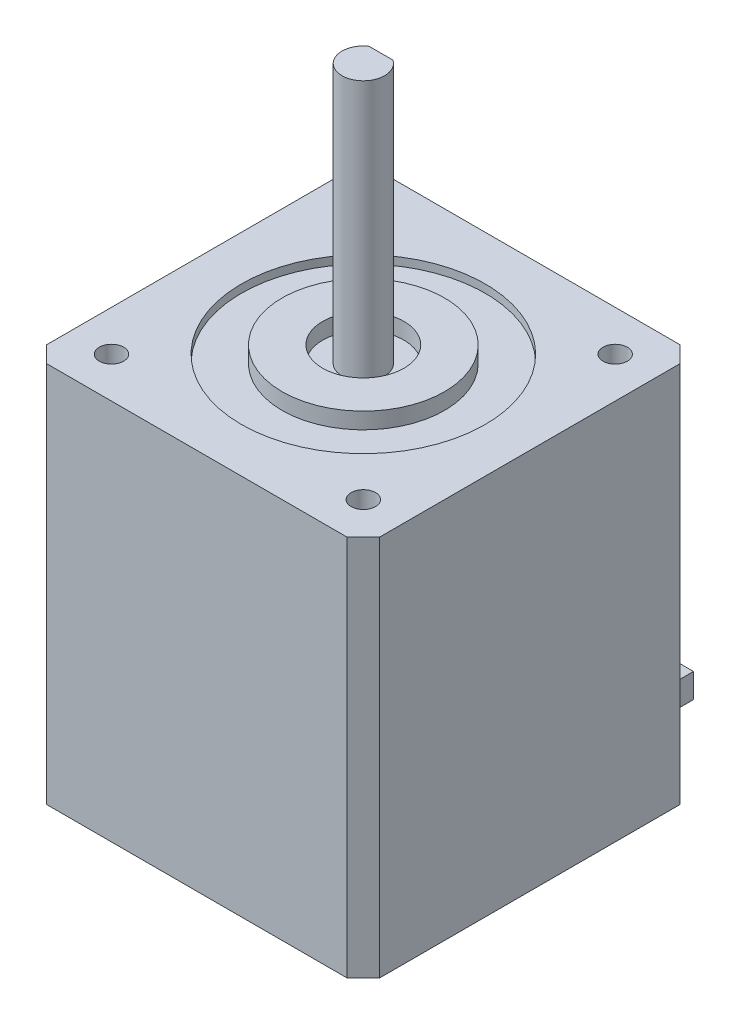
SolidWorks part; units mm, degrees
ref_plane "Front Plane" through (0, 0, 0) normal (0, 0, 1) x (1, 0, 0)
ref_plane "Top Plane" through (0, 0, 0) normal (0, 1, 0) x (1, 0, 0)
ref_plane "Right Plane" through (0, 0, 0) normal (1, 0, 0) x (0, 0, -1)
sketch "Sketch1" plane through (0, 0, 0) normal (0, 1, 0) x (1, 0, 0)
  line L0 (-20.5, 18.5) -> (-18.5, 20.5)
  line L1 (-18.5, -20.5) -> (18.5, -20.5)
  line L2 (-20.5, -18.5) -> (-20.5, 18.5)
  line L3 (-18.5, 20.5) -> (18.5, 20.5)
  line L4 (20.5, -18.5) -> (20.5, 18.5)
  line L5 (-20.5, -20.5) -> (20.5, 20.5) construction
  line L6 (-20.5, 20.5) -> (20.5, -20.5) construction
  line L7 (-18.5, -20.5) -> (-20.5, -18.5)
  line L8 (18.5, -20.5) -> (20.5, -18.5)
  line L9 (20.5, 18.5) -> (18.5, 20.5)
  point P0 (0, 0)
  dimension "D1" = 41
  dimension "D2" = 41
extrude "Boss-Extrude1" add sketch "Sketch1" along normal blind 47
sketch "Sketch2" plane through (0, 47, 0) normal (0, 1, 0) x (-1, 0, 0)
  circle A0 centre (0, 0) radius 15
extrude "Cut-Extrude1" cut sketch "Sketch2" against normal blind 1
sketch "Sketch3" plane through (0, 46, 0) normal (0, 1, 0) x (1, 0, 0)
  circle A0 centre (0, 0) radius 10
  circle A1 centre (0, 0) radius 5
extrude "Boss-Extrude2" add sketch "Sketch3" along normal blind 2
sketch "Sketch4" plane through (0, 46, 0) normal (0, 1, 0) x (1, 0, 0)
  line L0 (-1.471, 2.1754) -> (1.471, 2.1754)
  arc A0 (-1.471, 2.1754) -> (1.471, 2.1754) centre (0, 0) ccw
extrude "Boss-Extrude3" add sketch "Sketch4" along normal blind 32
hole_wizard "Ø3.0 (3) Diameter Hole1" positions "Sketch6" profile "Sketch5" hole size "Ø3.0" standard "Ansi Metric"
sketch "Sketch6" plane through (0, 47, 0) normal (0, 1, 0) x (-1, 0, 0)
  arc A0 (1.471, -2.1754) -> (-1.471, -2.1754) centre (0, 0) ccw construction
  point P0 (-15.5, -15.5)
  point P1 (15.5, -15.5)
  point P3 (15.5, 15.5)
  point P5 (-15.5, 15.5)
  dimension "D3" = 15.5
  dimension "D1" = 31
  dimension "D2" = 31
  dimension "D4" = 15.5
sketch "Sketch5" plane through (15.5, 47, -15.5) normal (1, 0, 0) x (0, 0, 1)
  line L0 (0, 0) -> (0, 5.9013)
  line L1 (0, 5.9013) -> (1.5, 5)
  line L2 (1.5, 5) -> (1.5, 0)
  line L5 (1.5, 0) -> (0, 0)
  line L10 (0, 5.9013) -> (-1.5, 5) construction
  line L11 (0, -6.35) -> (0, 107.95) construction
  dimension "Hole Dia." = 3
  dimension "Hole Depth" = 5
  dimension "Drill Angle" = 118
ref_axis "Motor Axis" through (0, 78, 0) along (0, -1, 0)
sketch "Sketch7" plane through (0, 0, -20.5) normal (0, 0, -1) x (-1, 0, 0)
  line L0 (-18.5, 0) -> (18.5, 0) construction
  line L1 (-10.1415, 0) -> (9.8585, 0)
  line L2 (-10.1415, 0) -> (-10.1415, 3)
  line L3 (-10.1415, 3) -> (9.8585, 3)
  line L4 (9.8585, 0) -> (9.8585, 3)
  dimension "D1" = 20
  dimension "D2" = 3
extrude "Boss-Extrude4" add sketch "Sketch7" along normal blind 10
